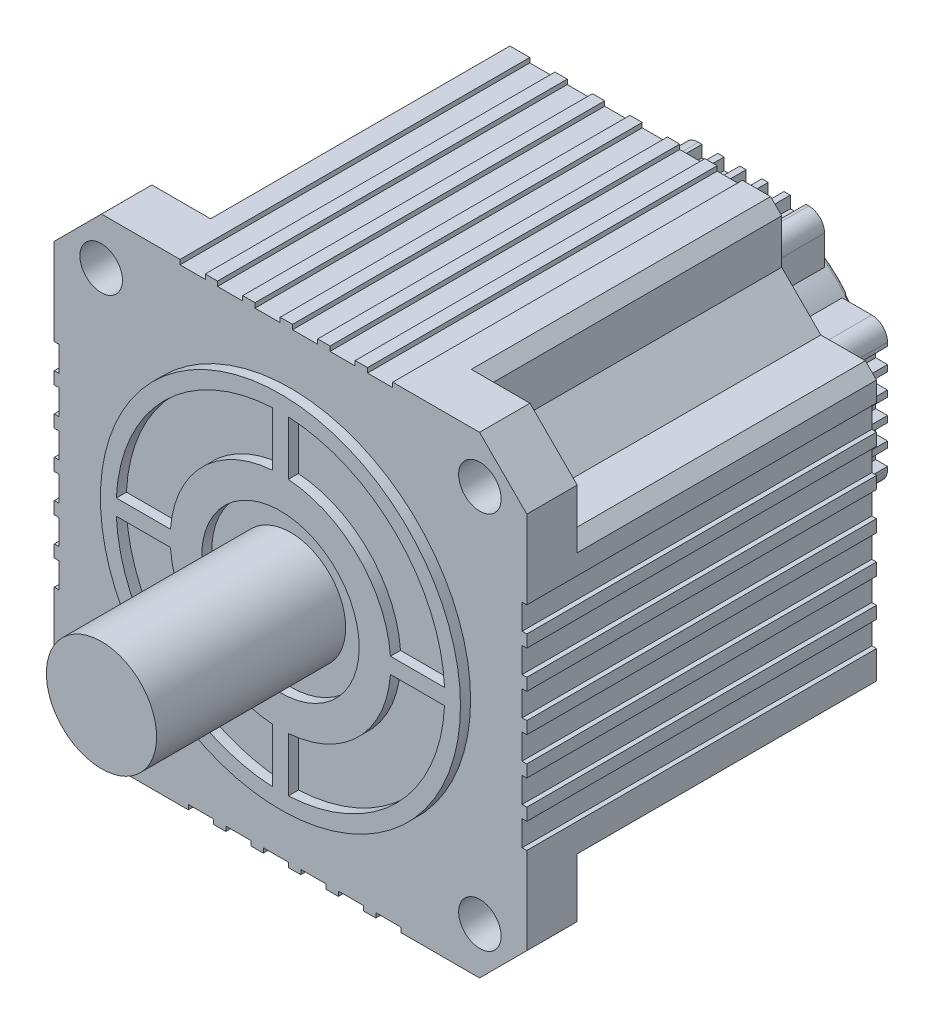
SolidWorks part; units mm, degrees
note: The reader was unsure of these and kept them because the rebuilt part matched: shared geometry of "草图16<3>".
ref_plane "前视基准面" through (0, 0, 0) normal (0, 0, 1) x (1, 0, 0)
ref_plane "上视基准面" through (0, 0, 0) normal (0, 1, 0) x (1, 0, 0)
ref_plane "右视基准面" through (0, 0, 0) normal (1, 0, 0) x (0, 0, -1)
sketch "草图1" plane through (0, 0, 0) normal (0, 0, 1) x (1, 0, 0)
  line L0 (-60, 75) -> (-75, 60)
  line L1 (-60, 75) -> (60, 75)
  line L2 (-75, 60) -> (-75, -60)
  line L3 (-60, -75) -> (60, -75)
  line L4 (75, 60) -> (75, -60)
  line L5 (-75, 75) -> (75, -75) construction
  line L6 (-75, -75) -> (75, 75) construction
  line L7 (60, 75) -> (75, 60)
  line L8 (75, -60) -> (60, -75)
  line L9 (-75, -60) -> (-60, -75)
  point P0 (0, 0)
  dimension "D1" = 150
  dimension "D2" = 150
extrude "拉伸1" add sketch "草图1" along normal blind 16
sketch "草图3" plane through (0, 0, 16) normal (0, 0, 1) x (1, 0, 0)
  line L0 (67.5, 67.5) -> (-67.5, -67.5) construction
  line L1 (75, 60) -> (60, 75) construction
  line L2 (-75, -60) -> (-60, -75) construction
  line L3 (-67.5, 67.5) -> (67.5, -67.5) construction
  line L4 (-60, 75) -> (-75, 60) construction
  line L5 (60, -75) -> (75, -60) construction
  circle A0 centre (0, 0) radius 100 construction
sketch "草图5" plane through (0, 0, 16) normal (0, 0, 1) x (1, 0, 0)
  circle A0 centre (0, 0) radius 57.15
  dimension "D1" = 114.3
extrude "拉伸2" add sketch "草图5" along normal blind 3.2
sketch "草图6" plane through (0, 0, 19.2) normal (0, 0, 1) x (1, 0, 0)
  circle A0 centre (0, 0) radius 52.15
  dimension "D1" = 104.3
extrude "拉伸3" cut sketch "草图6" against normal blind 3.2
sketch "草图7" plane through (0, 0, 16) normal (0, 0, 1) x (1, 0, 0)
  circle A0 centre (0, 0) radius 17.5
  dimension "D1" = 35
extrude "拉伸4" add sketch "草图7" along normal blind 60
sketch "草图9" plane through (0, 0, 16) normal (0, 0, 1) x (1, 0, 0)
  line L0 (0, 0) -> (102.718, 0) construction
  line L1 (25.0777, 2.5) -> (54.3657, 2.5)
  line L3 (25.0777, -2.5) -> (54.3657, -2.5)
  line L4 (54.3657, 2.5) -> (54.3657, -2.5)
  line L5 (25.0777, 2.5) -> (25.0777, -2.5)
  dimension "D1" = 2.5
  dimension "D2" = 2.5
extrude "拉伸5" add sketch "草图9" along normal blind 3.2
pattern_circular "阵列(圆周)1" count 4 over 360 about axis through (0, 0, 0) along (0, 0, 1) of "拉伸5"
sketch "草图10" plane through (0, 0, 16) normal (0, 0, 1) x (1, 0, 0)
  circle A0 centre (0, 0) radius 35
  circle A1 centre (0, 0) radius 25
extrude "拉伸6" add sketch "草图10" along normal blind 3.2
sketch "草图11" plane through (0, 0, 0) normal (0, 0, -1) x (-1, 0, 0)
  line L0 (-75, 41.3757) -> (-75, 11.8722)
  line L1 (-75, -60) -> (-75, 60) construction
  line L2 (75, 60) -> (75, -60) construction
  line L3 (11.8722, 75) -> (-41.3757, 75)
  line L4 (-60, 75) -> (60, 75) construction
  line L5 (-41.3757, 75) -> (-44.9113, 71.4645)
  line L6 (-71.4645, 44.9113) -> (-57.3223, 44.9113)
  line L7 (-57.3223, 44.9113) -> (-44.9113, 57.3223)
  line L8 (-44.9113, 57.3223) -> (-44.9113, 71.4645)
  line L9 (41.3757, 75) -> (11.8722, 75)
  line L10 (-71.4645, 44.9113) -> (-75, 41.3757)
  line L11 (44.9113, 71.4645) -> (41.3757, 75)
  line L12 (44.9113, 71.4645) -> (44.9113, 57.3223)
  line L13 (44.9113, 57.3223) -> (57.3223, 44.9113)
  line L14 (57.3223, 44.9113) -> (71.4645, 44.9113)
  line L15 (75, 41.3757) -> (71.4645, 44.9113)
  line L16 (75, -41.3757) -> (75, -11.8722)
  line L17 (71.4645, -44.9113) -> (75, -41.3757)
  line L18 (71.4645, -44.9113) -> (57.3223, -44.9113)
  line L19 (57.3223, -44.9113) -> (44.9113, -57.3223)
  line L20 (44.9113, -57.3223) -> (44.9113, -71.4645)
  line L21 (41.3757, -75) -> (44.9113, -71.4645)
  line L22 (-41.3757, -75) -> (-11.8722, -75)
  line L23 (-44.9113, -71.4645) -> (-41.3757, -75)
  line L24 (-44.9113, -71.4645) -> (-44.9113, -57.3223)
  line L25 (-44.9113, -57.3223) -> (-57.3223, -44.9113)
  line L26 (-57.3223, -44.9113) -> (-71.4645, -44.9113)
  line L29 (-75, -41.3757) -> (-71.4645, -44.9113)
  line L30 (-75, 11.8722) -> (-75, -41.3757)
  line L31 (75, 41.3757) -> (75, -11.8722)
  line L32 (-11.8722, -75) -> (41.3757, -75)
  point P2 (-75, 41.3757)
  point P7 (-71.4645, 44.9113)
  point P39 (-44.9113, 71.4645)
  point P42 (-41.3757, 75)
  dimension "D9" = 45
  dimension "D14" = 10
  dimension "D6" = 5
  dimension "D7" = 5
  dimension "D10" = 45
extrude "拉伸7" add sketch "草图11" along normal blind 95
sketch "草图12" plane through (0, 0, -95) normal (0, 0, -1) x (-1, 0, 0)
  line L0 (-42.5, -17.5) -> (-42.5, 17.5)
  line L1 (-17.5, -42.5) -> (17.5, -42.5)
  line L2 (42.5, -17.5) -> (42.5, 17.5)
  line L3 (22.5, 28.1066) -> (22.5, 37.4966)
  line L5 (-22.5, 28.1066) -> (-22.5, 37.4966)
  line L6 (-17.5, 42.4966) -> (17.5, 42.4966)
  line L10 (-28.1066, 22.5) -> (-37.5, 22.5)
  line L11 (37.5, 22.5) -> (28.1066, 22.5)
  line L12 (28.1066, -22.5) -> (37.5, -22.5)
  line L14 (22.5, -37.5) -> (22.5, -28.1066)
  line L15 (-22.5, -28.1066) -> (-22.5, -37.5)
  line L17 (-37.5, -22.5) -> (-28.1066, -22.5)
  line L23 (22.5, 28.1066) -> (22.5, 30) [skipped]
  arc A0 (-37.5, 22.5) -> (-42.5, 17.5) centre (-37.5, 17.5) ccw
  arc A1 (-17.5, 42.4966) -> (-22.5, 37.4966) centre (-17.5, 37.4966) ccw
  arc A2 (22.5, 37.4966) -> (17.5, 42.4966) centre (17.5, 37.4966) ccw
  arc A3 (42.5, 17.5) -> (37.5, 22.5) centre (37.5, 17.5) ccw
  arc A4 (37.5, -22.5) -> (42.5, -17.5) centre (37.5, -17.5) ccw
  arc A5 (17.5, -42.5) -> (22.5, -37.5) centre (17.5, -37.5) ccw
  arc A6 (-22.5, -37.5) -> (-17.5, -42.5) centre (-17.5, -37.5) ccw
  arc A7 (-42.5, -17.5) -> (-37.5, -22.5) centre (-37.5, -17.5) ccw
  arc A10 (28.1066, 22.5) -> (22.5, 28.1066) centre (0, 0) ccw
  arc A11 (22.5, -28.1066) -> (28.1066, -22.5) centre (0, 0) ccw
  arc A12 (-28.1066, -22.5) -> (-22.5, -28.1066) centre (0, 0) ccw
  arc A16 (-22.5, 28.1066) -> (-28.1066, 22.5) centre (0, 0) ccw
  point P6 (-22.5, 42.4966)
  point P11 (22.5, 42.4966)
  point P38 (-26.0355, 22.5)
  point P41 (-22.5, 26.0355)
  dimension "D1" = 5
  dimension "D2" = 14.39
  dimension "D4" = 5
  dimension "D3" = 14.39
  dimension "D8" = 5
extrude "拉伸8" add sketch "草图12" along normal blind 36
sketch "草图13" plane through (0, 0, -131) normal (0, 0, -1) x (-1, 0, 0)
  circle A0 centre (0, 0) radius 36.0032
extrude "拉伸9" add sketch "草图13" along normal blind 2
fillet "圆角5" radius 1 1 edges at (-36.0032, 0, -133)
sketch "草图14" plane through (0, 0, -95) normal (0, 0, -1) x (-1, 0, 0)
  line L0 (-32.4376, 73.5025) -> (-24.4376, 73.5025)
  line L2 (-24.4376, 73.5025) -> (-24.4376, 87.3537)
  line L3 (-24.4376, 87.3537) -> (-32.4376, 87.3537)
  line L5 (-32.4376, 87.3537) -> (-32.4376, 73.5025)
extrude "拉伸10" cut sketch "草图14" against normal blind 120
sketch "草图15" plane through (0, 0, -131) normal (0, 0, -1) x (-1, 0, 0)
  line L0 (-16.3794, -43.7336) -> (-16.3794, -38.7472)
  line L1 (-16.3794, -38.7472) -> (-11.3794, -38.7472)
  line L2 (-11.3794, -38.7472) -> (-11.3794, -43.7336)
  line L3 (-11.3794, -43.7336) -> (-16.3794, -43.7336)
  dimension "D1" = 5
extrude "拉伸11" cut sketch "草图15" against normal blind 44
pattern_linear "阵列(线性)4" count 5 spacing 7 along (-1, 0, 0) of "拉伸11"
sketch "草图16" plane through (0, 0, -133) normal (0, 0, -1) x (-1, 0, 0)
  line L0 (3.7784, 12.9251) -> (-4.4895, 12.9251)
  line L1 (-5.3556, 11.4251) -> (-2.0876, 5.7648)
  line L2 (-0.3556, 5.7648) -> (2.9124, 11.4251)
  line L3 (3.7784, 12.9251) -> (13.498, 12.9251)
  line L4 (3.7784, 13.9251) -> (13.2661, 13.9251)
  line L5 (-2.0876, 20.0854) -> (-10.3556, 5.7648)
  line L6 (-9.4895, 4.2648) -> (7.0464, 4.2648)
  line L7 (7.9124, 5.7648) -> (4.6444, 11.4251)
  line L8 (3.7784, 13.9251) -> (13.498, 13.9251) construction
  line L9 (2.9124, 14.4251) -> (-0.3556, 20.0854)
  line L10 (-6.7983, -9.8656) -> (-14.7983, -9.8656)
  line L11 (-15.7983, -10.8656) -> (-15.7983, -14.8656)
  line L12 (-14.7983, -15.8656) -> (-6.7983, -15.8656)
  line L13 (-6.7983, -15.8656) -> (-6.7983, -11.7903)
  line L14 (-6.7983, -11.7903) -> (-10.7983, -11.7903)
  line L15 (-10.7983, -11.7903) -> (-10.7983, -12.8656)
  line L16 (-10.7983, -12.8656) -> (-10.0983, -12.8656)
  line L17 (-9.7983, -13.1656) -> (-9.7983, -14.5656)
  line L18 (-10.0983, -14.8656) -> (-12.7983, -14.8656)
  line L19 (-12.7983, -14.8656) -> (-12.7983, -10.8656)
  line L20 (-12.7983, -10.8656) -> (-6.7983, -10.8656)
  line L21 (-6.7983, -10.8656) -> (-6.7983, -9.8656)
  line L22 (3.7341, -9.8656) -> (-4.2659, -9.8656)
  line L23 (-5.2659, -10.8656) -> (-5.2659, -12.8656)
  line L24 (-4.2659, -13.8656) -> (0.4341, -13.8656)
  line L25 (0.7341, -14.1656) -> (0.7341, -14.4491)
  line L26 (-5.2659, -14.7491) -> (0.4341, -14.7491)
  line L27 (-5.2659, -14.7491) -> (-5.2659, -15.8656)
  line L28 (-5.2659, -15.8656) -> (2.7341, -15.8656)
  line L29 (3.7341, -14.8656) -> (3.7341, -12.8656)
  line L30 (2.7341, -11.8656) -> (-1.9659, -11.8656)
  line L31 (-2.2659, -11.5656) -> (-2.2659, -11.1656)
  line L32 (-1.9659, -10.8656) -> (3.7341, -10.8656)
  line L33 (6.1202, -9.8656) -> (6.1202, -15.8656)
  line L34 (6.1202, -15.8656) -> (9.1202, -15.8656)
  line L35 (9.1202, -15.8656) -> (9.1202, -14.3656)
  line L36 (9.1202, -14.3656) -> (11.6916, -15.8656)
  line L37 (11.6916, -15.8656) -> (15.1202, -15.8656)
  line L38 (15.1202, -15.8656) -> (9.1202, -12.3656)
  line L39 (9.1202, -12.3656) -> (9.1202, -9.8656)
  line L40 (9.1202, -9.8656) -> (6.1202, -9.8656)
  line L41 (3.7341, -10.8656) -> (3.7341, -9.8656)
  circle A0 centre (-1.2216, 10.0383) radius 15
  arc A1 (3.7784, 13.9251) -> (2.9124, 14.4251) centre (3.7784, 14.9251) cw
  arc A2 (-0.3556, 20.0854) -> (-2.0876, 20.0854) centre (-1.2216, 19.5854) ccw
  arc A3 (-5.3556, 11.4251) -> (-4.4895, 12.9251) centre (-4.4895, 11.9251) cw
  arc A4 (-9.4895, 4.2648) -> (-10.3556, 5.7648) centre (-9.4895, 5.2648) cw
  arc A5 (7.9124, 5.7648) -> (7.0464, 4.2648) centre (7.0464, 5.2648) cw
  arc A6 (2.9124, 11.4251) -> (4.6444, 11.4251) centre (3.7784, 10.9251) cw
  arc A7 (-2.0876, 5.7648) -> (-0.3556, 5.7648) centre (-1.2216, 6.2648) ccw
  circle A8 centre (12.2447, -11.202) radius 1.5
  arc A9 (-14.7983, -15.8656) -> (-15.7983, -14.8656) centre (-14.7983, -14.8656) cw
  arc A10 (-14.7983, -9.8656) -> (-15.7983, -10.8656) centre (-14.7983, -10.8656) ccw
  arc A11 (-5.2659, -10.8656) -> (-4.2659, -9.8656) centre (-4.2659, -10.8656) cw
  arc A12 (-4.2659, -13.8656) -> (-5.2659, -12.8656) centre (-4.2659, -12.8656) cw
  arc A13 (3.7341, -12.8656) -> (2.7341, -11.8656) centre (2.7341, -12.8656) ccw
  arc A14 (2.7341, -15.8656) -> (3.7341, -14.8656) centre (2.7341, -14.8656) ccw
  arc A15 (-1.9659, -10.8656) -> (-2.2659, -11.1656) centre (-1.9659, -11.1656) ccw
  arc A16 (-1.9659, -11.8656) -> (-2.2659, -11.5656) centre (-1.9659, -11.5656) cw
  arc A17 (0.7341, -14.1656) -> (0.4341, -13.8656) centre (0.4341, -14.1656) ccw
  arc A18 (0.4341, -14.7491) -> (0.7341, -14.4491) centre (0.4341, -14.4491) ccw
  arc A19 (-9.7983, -13.1656) -> (-10.0983, -12.8656) centre (-10.0983, -13.1656) ccw
  arc A20 (-9.7983, -14.5656) -> (-10.0983, -14.8656) centre (-10.0983, -14.5656) cw
  point P3 (-1.2216, 10.0383)
  point P16 (3.2011, 13.9251)
  point P88 (-9.7983, -12.8656)
  point P91 (-9.7983, -14.8656)
  dimension "D1" = 30
  dimension "D3" = 1
  dimension "D29" = 3
  dimension "D31" = 1
  dimension "D32" = 1
  dimension "D33" = 0.3
  dimension "D2" = 1
  dimension "D4" = 6
  dimension "D5" = 6
  dimension "D6" = 1
  dimension "D7" = 6
  dimension "D8" = 9
  dimension "D9" = 9
  dimension "D10" = 9
  dimension "D11" = 3
  dimension "D12" = 1
  dimension "D13" = 3
  dimension "D14" = 1
  dimension "D15" = 1
  dimension "D16" = 3
  dimension "D17" = 3
  dimension "D18" = 2
  dimension "D19" = 3
  dimension "D20" = 9
  dimension "D21" = 1.5
  dimension "D22" = 3
  dimension "D23" = 2
  dimension "D24" = 1
  dimension "D26" = 6
  dimension "D30" = 2
extrude "拉伸12" add sketch "草图16" along normal blind 2 contours L1 A7 L2 A6 L7 A5 L6 A4 L5 A2 L9 A1 L4 A0 L3 L0 A3
extrude "拉伸13" add sketch "草图16<3>" along normal blind 2 contours L17 A20 L18 L19 L20 L21 L10 A10 L11 A9 L12 L13 L14 L15 L16 A19 | A18 L26 L27 L28 A14 L29 A13 L30 A16 L31 A15 L32 L41 L22 A11 L23 A12 L24 A17 L25 | L33 L34 L35 L36 L37 L38 L39 L40 | A8
sketch "草图16<3>" plane through (0, 0, -133) normal (0, 0, -1) x (-1, 0, 0) same geometry as "草图16"
pattern_linear "阵列(线性)3" count 6 spacing 11.9 along (-1, 0, 0) of "拉伸10"
pattern_circular "阵列(圆周)2" count 4 over 360 about axis through (0, 0, 0) along (0, 0, 1) of "阵列(线性)3", "拉伸10"
pattern_circular "阵列(圆周)3" count 4 every 90 about axis through (0, 0, 0) along (0, 0, 1) of "拉伸11", "阵列(线性)4"
sketch "草图17" plane through (0, 0, 16) normal (0, 0, 1) x (1, 0, 0)
  line L0 (-67.5, 67.5) -> (67.5, -67.5) construction
  line L1 (-60, 75) -> (-75, 60) construction
  line L2 (60, -75) -> (75, -60) construction
  line L3 (67.5, -67.5) -> (-67.5, -67.5) construction
  line L4 (-75, -60) -> (-60, -75) construction
  line L5 (-67.5, -67.5) -> (67.5, 67.5) construction
  line L6 (75, 60) -> (60, 75) construction
  circle A0 centre (0, 0) radius 85 construction
  circle A1 centre (-60.1041, 60.1041) radius 6.75
  circle A2 centre (60.1041, 60.1041) radius 6.75
  circle A3 centre (60.1041, -60.1041) radius 6.75
  circle A4 centre (-60.1041, -60.1041) radius 6.75
  dimension "D1" = 170
  dimension "D2" = 13.5
  dimension "D3" = 13.5
  dimension "D4" = 13.5
  dimension "D5" = 13.5
extrude "拉伸15" cut sketch "草图17" against normal blind 30
